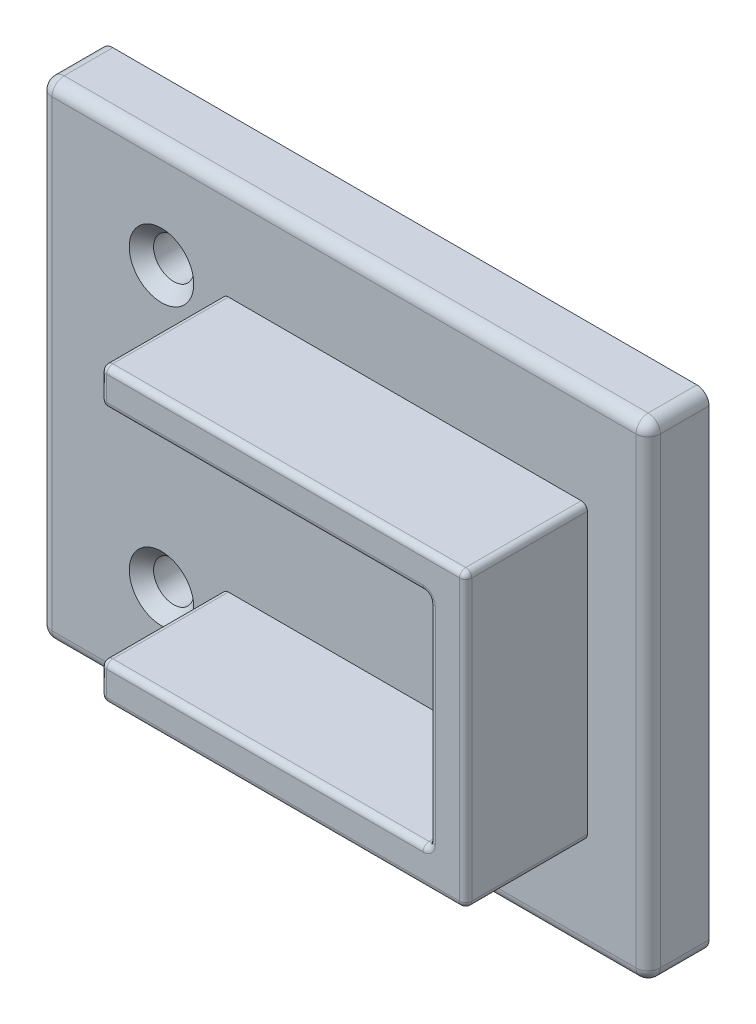
SolidWorks part; units mm, degrees
ref_plane "前视基准面" through (0, 0, 0) normal (0, 0, 1) x (1, 0, 0)
ref_plane "上视基准面" through (0, 0, 0) normal (0, 1, 0) x (1, 0, 0)
ref_plane "右视基准面" through (0, 0, 0) normal (1, 0, 0) x (0, 0, -1)
other "Configuration Table"
sketch "草图2" plane through (0, 0, 0) normal (0, 0, 1) x (1, 0, 0)
  line L1 (25, 20) -> (-25, 20)
  line L2 (25, 20) -> (25, -20)
  line L3 (25, -20) -> (-25, -20)
  line L4 (-25, 20) -> (-25, -20)
  line L5 (88, 0) -> (-32, 0) construction
  dimension "D1" = 40
  dimension "D2" = 50
  dimension "D3" = 25
extrude "凸台-拉伸1" add sketch "草图2" along normal blind 5
sketch "草图5" plane through (0, -20, 0) normal (0, -1, 0) x (1, 0, 0)
  line L0 (20, 5) -> (20, 15)
  line L1 (-25, 5) -> (25, 5) construction
  line L2 (20, 15) -> (-10, 15)
  line L3 (-10, 15) -> (-10, 5)
  line L4 (-10, 5) -> (20, 5)
  line L5 (25, 5) -> (25, 0) construction
  dimension "D1" = 30
  dimension "D2" = 10
  dimension "D3" = 90
  dimension "D4" = 5
extrude "凸台-拉伸2" add sketch "草图5" against normal blind 3 from offset 8 offset against normal yes
sketch "草图6" plane through (0, 20, 0) normal (0, 1, 0) x (1, 0, 0)
  line L4 (20, -15) -> (20, -5)
  line L5 (-10, -15) -> (20, -15)
  line L6 (-10, -5) -> (-10, -15)
  line L7 (20, -5) -> (-10, -5)
  line L8 (20, -15) -> (20, -5)
  line L9 (-10, -15) -> (20, -15)
  line L10 (-10, -5) -> (-10, -15)
  line L11 (20, -5) -> (-10, -5)
  dimension "D1" = 0
extrude "凸台-拉伸3" add sketch "草图6" against normal blind 3 from offset 8 offset against normal yes
sketch "草图7" plane through (0, 0, 0) normal (0, 0, -1) x (-1, 0, 0)
  line L0 (0, 0) -> (-49464.6492, 0) construction
  circle A4 centre (-10, 0) radius 1.65
  circle A5 centre (15, -11.5) radius 1.65
  circle A6 centre (15, 11.5) radius 1.65
  dimension "D1" = 3.3
  dimension "D2" = 25
  dimension "D3" = 11.5
  dimension "D4" = 11.5
  dimension "D5" = 10
extrude "切除-拉伸1" cut sketch "草图7" against normal up to next
fillet "圆角3" radius 1 8 edges at (0, -20, 5) (-25, 0, 5) (0, 20, 5) (25, 0, 5) (-25, -20, 2.5) (-25, 20, 2.5) (25, 20, 2.5) (25, -20, 2.5)
sketch "草图8" plane through (20, 0, 0) normal (1, 0, 0) x (0, 0, -1)
  line L1 (-15, 9) -> (-5, 9)
  line L2 (-15, 9) -> (-15, -12)
  line L3 (-15, -12) -> (-5, -12)
  line L4 (-5, 9) -> (-5, -12)
extrude "凸台-拉伸4" add sketch "草图8" against normal blind 3
fillet "圆角4" radius 0.5 16 edges at (3.5, 9, 15) (-10, 10.5, 15) (5, 12, 15) (20, 0, 15) (5, -12, 15) (-10, -10.5, 15) (3.5, -9, 15) (17, 0, 15) (17, -9, 10) (-10, -9, 10) (-10, -12, 10) (20, 12, 10) (-10, 12, 10) (-10, 9, 10) (17, 9, 10) (20, -12, 10)
chamfer "倒角1" distance 1 angle 45 6 edges at (-16.65, 11.5, 5) (-16.65, 11.5, 0) (-16.65, -11.5, 5) (-16.65, -11.5, 0) (8.35, 0, 5) (8.35, 0, 0)
